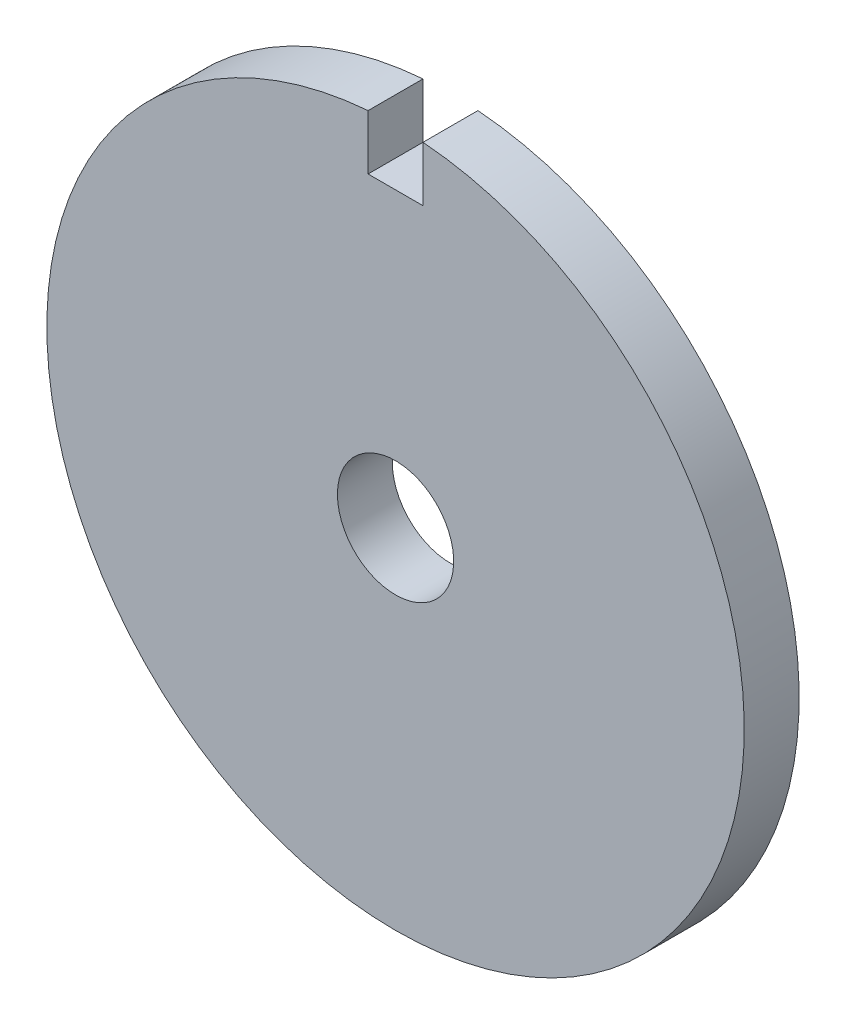
SolidWorks part; units mm, degrees
ref_plane "Front Plane" through (0, 0, 0) normal (0, 0, 1) x (1, 0, 0)
ref_plane "Top Plane" through (0, 0, 0) normal (0, 1, 0) x (1, 0, 0)
ref_plane "Right Plane" through (0, 0, 0) normal (1, 0, 0) x (0, 0, -1)
sketch "Sketch1" plane through (0, 0, 0) normal (0, 0, 1) x (1, 0, 0)
  circle A0 centre (0, 0) radius 12.7
  circle A1 centre (0, 0) radius 3.175
  circle A2 centre (0, 0) radius 19.05
  dimension "D1" = 25.4
  dimension "D2" = 6.35
  dimension "D3" = 38.1
extrude "Boss-Extrude1" add sketch "Sketch1" along normal blind 2.9997 contours A0 A1 region at (-12.3408, 0, 0)
extrude "Boss-Extrude2" add sketch "Sketch1<4>" along normal up to surface (2.9997 mm away) contours A2 A0 region at (-18.5112, 0, 0) up to face at (3.175, 0, 2.9997)
sketch "Sketch1<4>" plane through (0, 0, 0) normal (0, 0, 1) x (1, 0, 0) same geometry as "Sketch1"
sketch "Sketch2" plane through (0, 0, 0) normal (0, 0, -1) x (-1, 0, 0)
  line L1 (-1.5, 18.9909) -> (1.5, 18.9909)
  line L2 (-1.5, 18.9909) -> (-1.5, 15.9909)
  line L3 (-1.5, 15.9909) -> (1.5, 15.9909)
  line L4 (1.5, 18.9909) -> (1.5, 15.9909)
  circle A0 centre (0, 0) radius 19.05 construction
  point P4 (0, 15.9909)
  circle M6 centre (0, 0) radius 19.05
  dimension "D1" = 3
extrude "Cut-Extrude1" cut sketch "Sketch2" against normal through all both and the other way through all contours L4 L1 L2 L3 | M6 | L1 M6 region at (0, 19.0145, 0) region at (0, 17.4909, 0)
equation "\"thick\"= 6mm"
equation "\"dowel\"= 1 / 4"
equation "\"D2@Sketch1\"=\"dowel\""
equation "\"D1@Sketch1\"=\"dowel\"*4"
equation "\"D3@Sketch1\"=\"dowel\"*6"
equation "\"D1@Sketch2\"=3mm"
